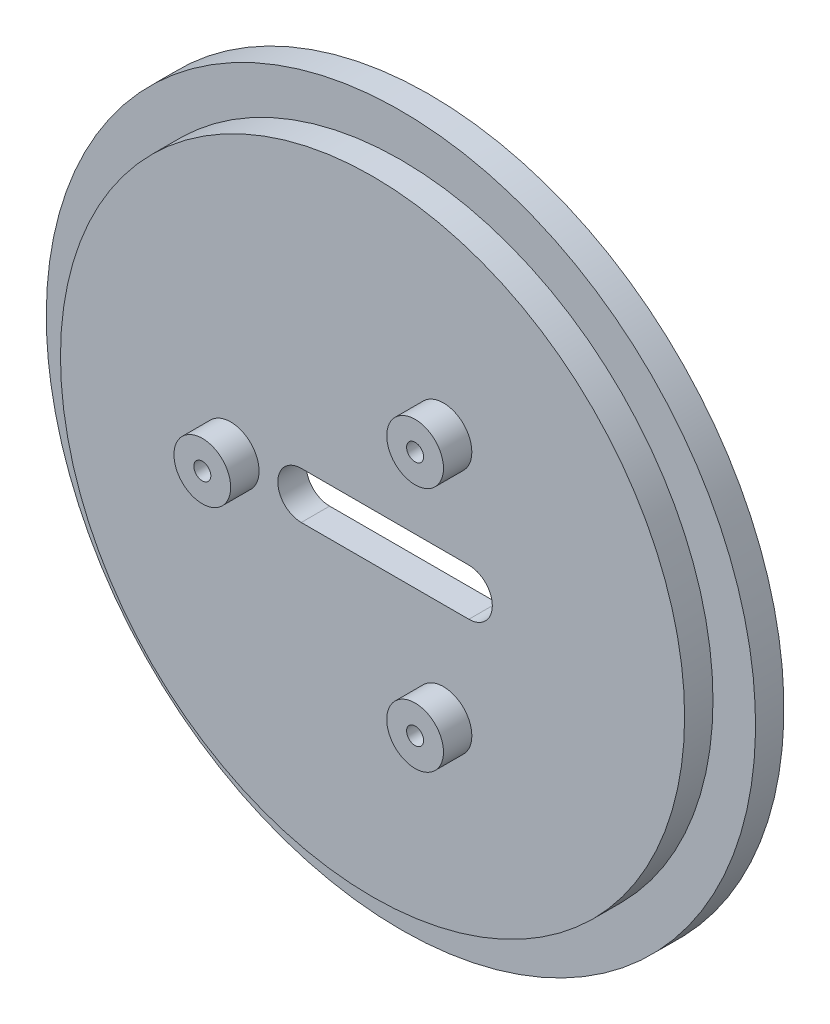
SolidWorks part; units mm, degrees
ref_plane "前视基准面" through (0, 0, 0) normal (0, 0, 1) x (1, 0, 0)
ref_plane "上视基准面" through (0, 0, 0) normal (0, 1, 0) x (1, 0, 0)
ref_plane "右视基准面" through (0, 0, 0) normal (1, 0, 0) x (0, 0, -1)
sketch "草图1" plane through (0, 0, 0) normal (0, 0, 1) x (1, 0, 0)
  circle A0 centre (0, 0) radius 22
extrude "凸台-拉伸1" add sketch "草图1" along normal blind 2
sketch "草图2" plane through (0, 0, 2) normal (0, 0, 1) x (1, 0, 0)
  circle A1 centre (-10, 0) radius 0.6
  circle A2 centre (5, -8.6603) radius 0.6
  circle A3 centre (5, 8.6603) radius 0.6
  circle A4 centre (-10, 0) radius 2
  circle A5 centre (5, 8.6603) radius 2
  circle A6 centre (5, -8.6603) radius 2
extrude "凸台-拉伸2" add sketch "草图2" along normal blind 4
sketch "草图3" plane through (0, 0, 0) normal (0, 0, -1) x (-1, 0, 0)
  circle A0 centre (0, 0) radius 25
extrude "凸台-拉伸3" add sketch "草图3" along normal blind 2
sketch "草图4" plane through (0, 0, -2) normal (0, 0, -1) x (-1, 0, 0)
  line L1 (-7.25, 3.95) -> (7.25, 3.95)
  line L3 (-7.25, -3.95) -> (7.25, -3.95)
  arc A2 (-7.25, 3.95) -> (-7.25, -3.95) centre (-7.25, 0) ccw
  arc A3 (7.25, 3.95) -> (7.25, -3.95) centre (7.25, 0) cw
  point P8 (0, 3.95)
  point P11 (0, -3.95)
extrude "切除-拉伸1" cut sketch "草图4" against normal blind 2
sketch "草图5" plane through (0, 0, -2) normal (0, 0, -1) x (-1, 0, 0)
  line L0 (21, -3.95) -> (21, -4)
  line L2 (21, -4) -> (29.149, -4)
  line L7 (29.149, -4) -> (29.149, 4)
  line L10 (21, -3.95) -> (21, 4)
  line L12 (29.149, 4) -> (21, 4)
extrude "切除-拉伸2" cut sketch "草图5" against normal blind 1
sketch "草图6" plane through (0, 0, -2) normal (0, 0, -1) x (-1, 0, 0)
  circle A2 centre (-18, 0) radius 5.45
  circle A3 centre (9, 15.5885) radius 5.45
  circle A4 centre (9, -15.5885) radius 5.45
  circle A5 centre (-18, 0) radius 3.85
  circle A6 centre (9, 15.5885) radius 3.85
  circle A7 centre (9, -15.5885) radius 3.85
  dimension "D1" = 3
extrude "切除-拉伸3" cut sketch "草图6" against normal blind 1.3
sketch "草图8" plane through (0, 0, 6) normal (0, 0, 1) x (1, 0, 0)
  circle A0 centre (5, -8.6603) radius 0.6
  circle A1 centre (-10, 0) radius 0.6
  circle A2 centre (5, 8.6603) radius 0.6
extrude "切除-拉伸4" cut sketch "草图8" against normal blind 18.5
sketch "草图9" plane through (0, 0, 6) normal (0, 0, 1) x (1, 0, 0)
  circle A0 centre (0, 0) radius 16.6958
extrude "切除-拉伸5" cut sketch "草图9" against normal blind 2
sketch "草图10" plane through (0, 0, -2) normal (0, 0, -1) x (-1, 0, 0)
  circle A0 centre (-5, -8.6603) radius 1.6
  circle A1 centre (-5, 8.6603) radius 1.6
extrude "切除-拉伸6" cut sketch "草图10" against normal blind 1
sketch "草图11" plane through (0, 0, -2) normal (0, 0, -1) x (-1, 0, 0)
  circle A0 centre (10, 0) radius 1.6
extrude "切除-拉伸7" cut sketch "草图11" against normal blind 3
sketch "草图12" plane through (0, 0, 0) normal (0, 0, -1) x (-1, 0, 0)
  line L0 (5.0257, 0) -> (-6.7903, 0) construction
  line L1 (5.0257, -1.6529) -> (-6.7903, -1.6529)
  line L2 (5.0257, 1.6529) -> (-6.7903, 1.6529)
  arc A0 (5.0257, -1.6529) -> (5.0257, 1.6529) centre (5.0257, 0) ccw
  arc A1 (-6.7903, 1.6529) -> (-6.7903, -1.6529) centre (-6.7903, 0) ccw
  point P3 (-0.8823, 0)
  point P8 (5.0257, 0)
extrude "切除-拉伸8" cut sketch "草图12" against normal blind 10
